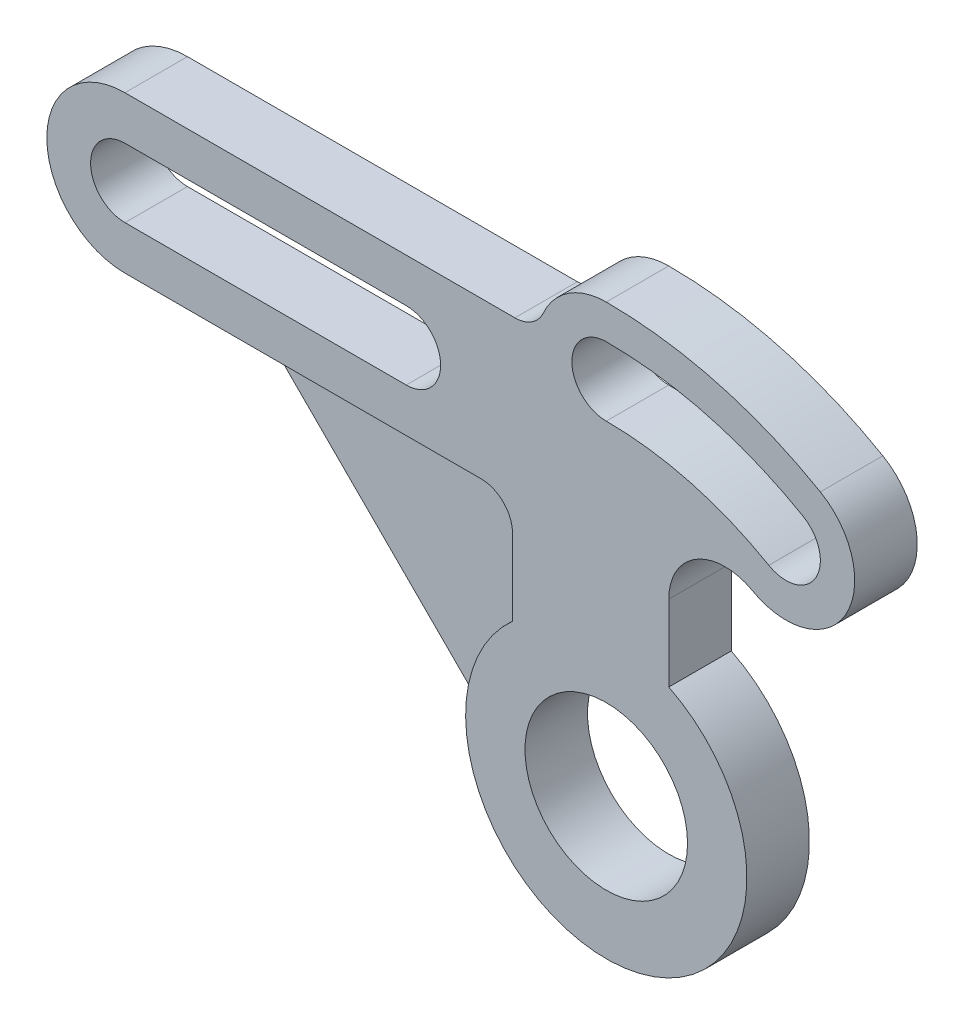
SolidWorks part; units mm, degrees
ref_plane "前视基准面" through (0, 0, 0) normal (0, 0, 1) x (1, 0, 0)
ref_plane "上视基准面" through (0, 0, 0) normal (0, 1, 0) x (1, 0, 0)
ref_plane "右视基准面" through (0, 0, 0) normal (1, 0, 0) x (0, 0, -1)
other "Configuration Table"
sketch "草图1" plane through (0, 0, 0) normal (0, 0, 1) x (1, 0, 0)
  line L0 (0, 210.6134) -> (0, -210.6134) construction
  line L1 (-303.6559, 0) -> (303.6559, 0) construction
  line L2 (-30, -35) -> (-30, -59.459)
  line L3 (20, -28.3263) -> (20, -52.6887)
  line L4 (-154, 11) -> (-64, 11)
  line L5 (-154, -11) -> (-64, -11)
  line L6 (-154, 25) -> (-29.2404, 25)
  line L7 (-154, -25) -> (-40, -25)
  line L8 (0, -93) -> (85.7103, 55.4545) construction
  line L9 (-113, -25) -> (-45, -93)
  circle A0 centre (0, -93) radius 26
  arc A1 (-30, -59.459) -> (20, -52.6887) centre (0, -93) ccw
  arc A2 (-154, 11) -> (-154, -11) centre (-154, 0) ccw
  arc A3 (-154, 25) -> (-154, -25) centre (-154, 0) ccw
  arc A4 (-64, -11) -> (-64, 11) centre (-64, 0) ccw
  arc A5 (-29.2404, 25) -> (-20.1028, 30.9375) centre (-29.2404, 35) ccw
  arc A6 (0, 22) -> (57.5, 6.5929) centre (0, -93) cw construction
  arc A7 (63, 16.1192) -> (0, 33) centre (0, -93) ccw
  arc A8 (52, -2.9334) -> (0, 11) centre (0, -93) ccw
  arc A9 (52, -2.9334) -> (63, 16.1192) centre (57.5, 6.5929) ccw
  arc A10 (0, 33) -> (0, 11) centre (0, 22) ccw
  arc A11 (68.5, 25.6455) -> (0, 44) centre (0, -93) ccw
  arc A12 (0, 44) -> (-20.1028, 30.9375) centre (0, 22) ccw
  arc A14 (46.5, -12.4596) -> (68.5, 25.6455) centre (57.5, 6.5929) ccw
  arc A15 (0, 44) -> (0, 0) centre (0, 22) ccw construction
  arc A16 (46.5, -12.4596) -> (0, 0) centre (0, -93) ccw construction
  arc A17 (-40, -25) -> (-30, -35) centre (-40, -35) cw
  arc A18 (46.5, -12.4596) -> (20, -28.3263) centre (38, -28.3263) ccw
  point P27 (29.7642, 18.0815)
  dimension "D1" = 90
  dimension "D2" = 52
  dimension "D6" = 50
  dimension "D7" = 22
  dimension "D8" = 22
  dimension "D10" = 10
  dimension "D15" = 11
  dimension "D16" = 83
  dimension "D18" = 10
  dimension "D19" = 18
  dimension "D3" = 93
  dimension "D4" = 30
  dimension "D5" = 20
  dimension "D9" = 90
  dimension "D11" = 30
  dimension "D13" = 115
  dimension "D14" = 154
  dimension "D17" = 45
  dimension "D12" = 11
extrude "凸台-拉伸1" add sketch "草图1" along normal mid plane 20 contours A18 A14 A11 A12 A5 L6 A3 L7 A17 L2 A1 L3 A10 A7 A9 A8 A4 L5 A2 L4 A0 region at (-28.8749, -28.8002, 0)
extrude "凸台-拉伸2" add sketch "草图1<3>" along normal mid plane 10 contours A17 L7 L9 A1 L2 region at (-61.2496, -47.9034, 0)
sketch "草图1<3>" plane through (0, 0, 0) normal (0, 0, 1) x (1, 0, 0) same geometry as "草图1"
fillet "圆角1" radius 18 2 edges at (-113, -25, 0) (-45, -93, 0)
